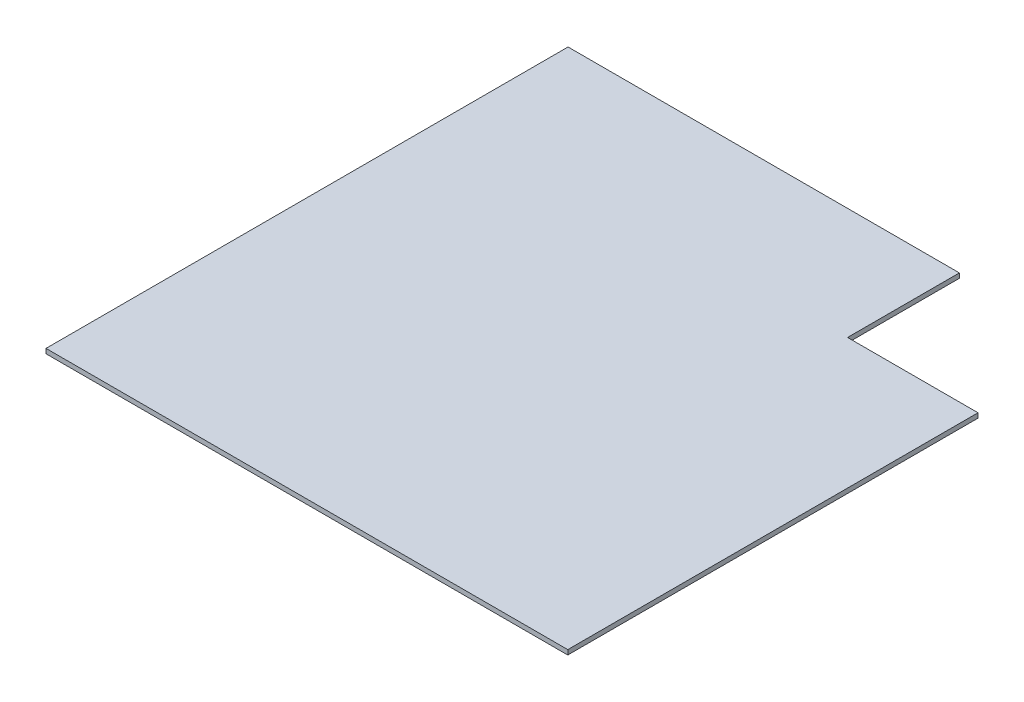
SolidWorks part; units mm, degrees
ref_plane "Front Plane" through (0, 0, 0) normal (0, 0, 1) x (1, 0, 0)
ref_plane "Top Plane" through (0, 0, 0) normal (0, 1, 0) x (1, 0, 0)
ref_plane "Right Plane" through (0, 0, 0) normal (1, 0, 0) x (0, 0, -1)
sketch "Sketch1" plane through (0, 0, 0) normal (0, 1, 0) x (1, 0, 0)
  line L0 (-130.625, 184.7613) -> (351.9808, 184.7613) construction
  line L1 (167.8286, 0.5153) -> (345.6286, 0.5153)
  line L2 (167.8286, 0.5153) -> (167.8286, 178.4113)
  line L3 (167.8286, 178.4113) -> (301.1786, 178.4113)
  line L4 (345.6286, 0.5153) -> (345.6286, 140.3113)
  line L19 (345.6286, 140.3113) -> (301.1786, 140.3113)
  line L20 (301.1786, 178.4113) -> (301.1786, 140.3113)
  line L21 (351.9786, 184.7613) -> (351.9786, -3.4747) construction
  line L22 (351.9808, -5.8347) -> (-130.625, -5.8347) construction
  point P1 (0, 0)
  dimension "D1" = 6.35
  dimension "D2" = 184.15
  dimension "D3" = 6.35
  dimension "D4" = 6.35
  dimension "D5" = 177.8
  dimension "D6" = 38.1
  dimension "D8" = 44.45
extrude "Boss-Extrude1" add sketch "Sketch1" along normal blind 1.6002 contours L1 L20 L19 L4 L3 L2 region at (252.9567, 0, -85.509)
